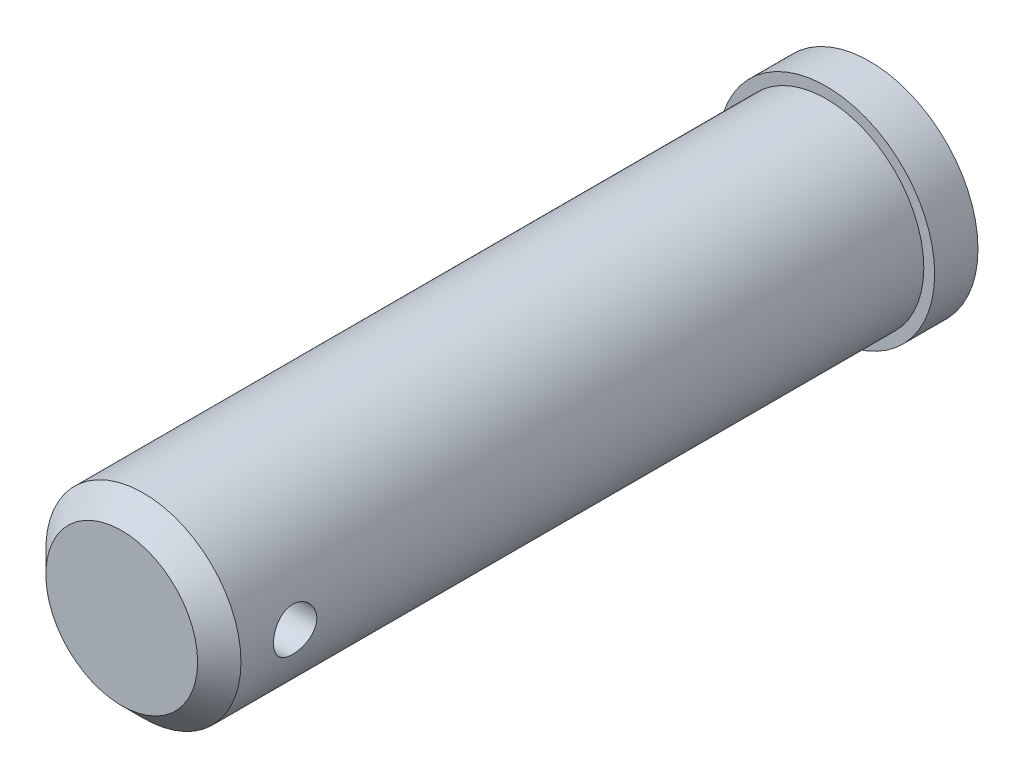
SolidWorks part; units mm, degrees
ref_plane "Front Plane" through (0, 0, 0) normal (0, 0, 1) x (1, 0, 0)
ref_plane "Top Plane" through (0, 0, 0) normal (0, 1, 0) x (1, 0, 0)
ref_plane "Right Plane" through (0, 0, 0) normal (1, 0, 0) x (0, 0, -1)
sketch "Sketch1" plane through (0, 0, 0) normal (0, 0, 1) x (1, 0, 0)
  circle A0 centre (0, 0) radius 10
  dimension "D1" = 20
extrude "Boss-Extrude1" add sketch "Sketch1" along normal blind 4
sketch "Sketch2" plane through (0, 0, 4) normal (0, 0, 1) x (1, 0, 0)
  circle A0 centre (0, 0) radius 9
  dimension "D1" = 18
extrude "Boss-Extrude2" add sketch "Sketch2" along normal blind 65
fillet "Chamfer4" radius 2 1 edges at (9, 0, 69) type face fillet profile chamfer first side face at (9, 0, 69) second side face at (9, 0, 69)
sketch "Sketch3" plane through (0, 0, 0) normal (1, 0, 0) x (0, 0, -1)
  line L0 (-4, 9) -> (-4, -9) construction
  circle A0 centre (-62, 0) radius 2
  point P4 (0, 0)
  dimension "D1" = 4
  dimension "D2" = 58
  dimension "D3" = 9
extrude "Cut-Extrude1" cut sketch "Sketch3" against normal mid plane 65
